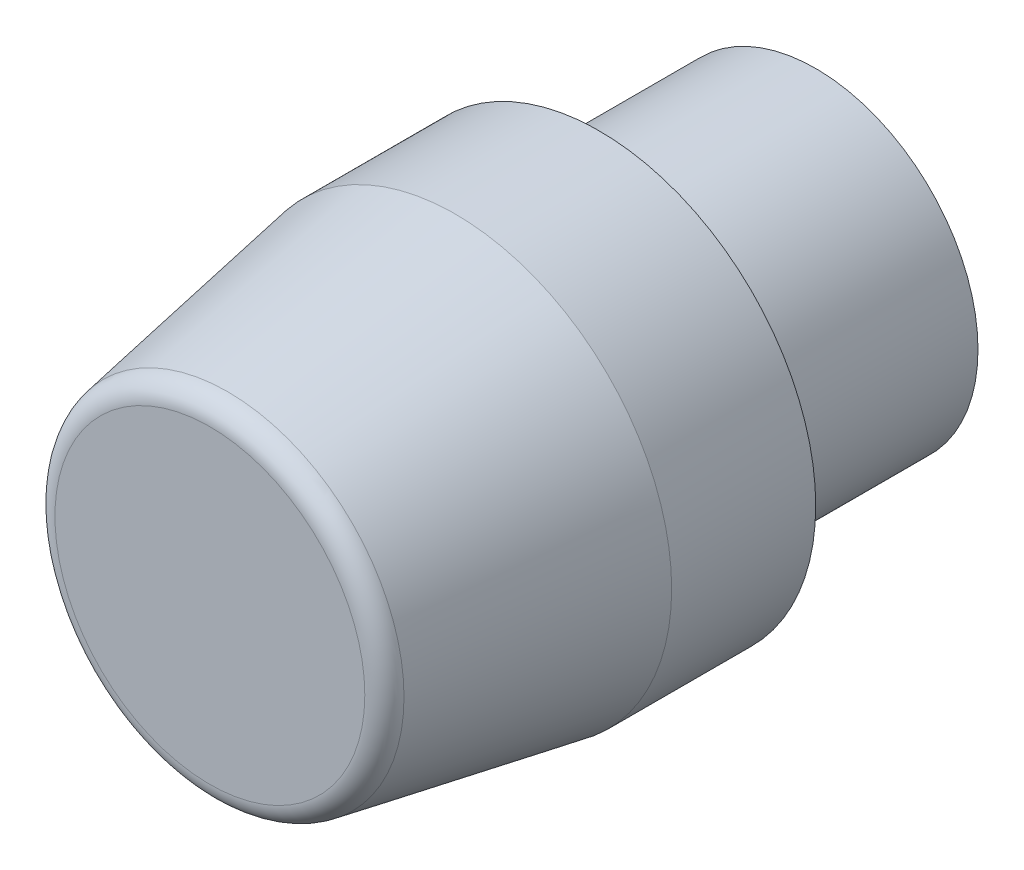
SolidWorks part; units mm, degrees
ref_plane "Front Plane" through (0, 0, 0) normal (0, 0, 1) x (1, 0, 0)
ref_plane "Top Plane" through (0, 0, 0) normal (0, 1, 0) x (1, 0, 0)
ref_plane "Right Plane" through (0, 0, 0) normal (1, 0, 0) x (0, 0, -1)
sketch "Sketch1" plane through (0, 0, 0) normal (0, 0, 1) x (1, 0, 0)
  circle A0 centre (0, 0) radius 7.5
extrude "Boss-Extrude1" add sketch "Sketch1" along normal blind 10
sketch "Sketch2" plane through (0, 0, 10) normal (0, 0, 1) x (1, 0, 0)
  circle A0 centre (0, 0) radius 10
extrude "Boss-Extrude2" add sketch "Sketch2" along normal blind 18
chamfer "Chamfer1" distance 2 angle 80 1 edges at (10, 0, 28) first distance on face at (10, 0, 28)
fillet "Скругление1" radius 1 1 edges at (8, 0, 28)
